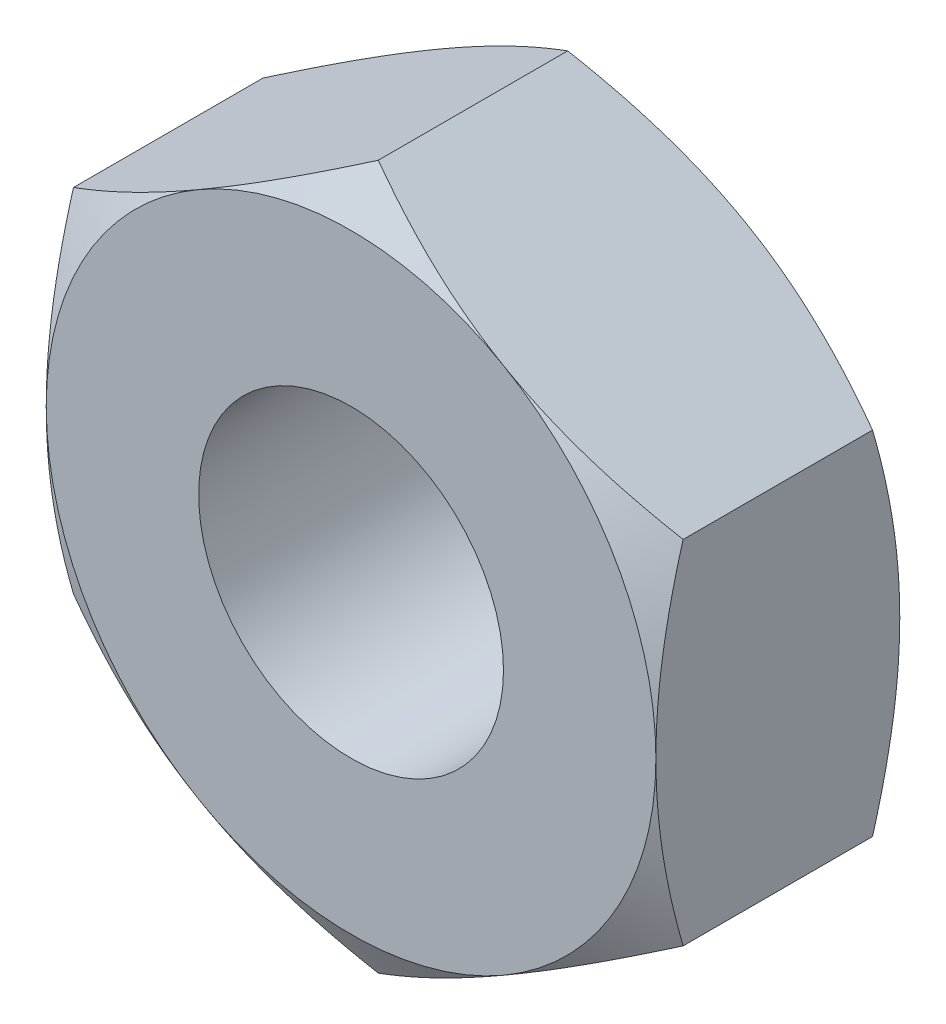
SolidWorks part; units mm, degrees
ref_plane "Front Plane" through (0, 0, 0) normal (0, 0, 1) x (1, 0, 0)
ref_plane "Top Plane" through (0, 0, 0) normal (0, 1, 0) x (1, 0, 0)
ref_plane "Right Plane" through (0, 0, 0) normal (1, 0, 0) x (0, 0, -1)
sketch "Sketch1" plane through (0, 0, 0) normal (1, 0, 0) x (0, 0, -1)
  line L0 (-1, 0) -> (1, 0) construction
  line L1 (-1, -2.5) -> (-1, 2.5) construction
  line L2 (1, -2.5) -> (1, 2.5) construction
  line L3 (-1, -1.25) -> (-1, 1.25) construction
  line L4 (-1.4219, 1.2987) -> (-1.1969, 0.909) construction
  line L5 (-1.1969, 0.909) -> (-0.9719, 1.2987) construction
  line L6 (-0.9719, 1.2987) -> (-1.4219, 1.2987) construction
  line L7 (-1.4078, 1.2744) -> (-0.9859, 1.2744) construction
  line L8 (-1.3938, 1.25) -> (-1, 1.25) construction
  line L9 (-1.225, 0.9577) -> (-1.1688, 0.9577) construction
  line L10 (-1.1969, 0.9577) -> (-1.1969, 0.909) construction
  line L11 (-1.1969, 1.2987) -> (-1.1969, 1.25) construction
  point P4 (0, 0)
  point P7 (-1, 0)
  point P11 (1, 0)
  point P14 (-1, 0)
  point P26 (-1.1969, 1.2744)
  point P27 (-1, -1.25)
  dimension "Height" = 2
  dimension "Width" = 5
  dimension "Thread OD" = 2.5
  dimension "D1" = 60
  dimension "Pitch" = 0.45
  dimension "D2" = 0.0562
sketch "Sketch2" plane through (0, 0, 0) normal (0, 0, 1) x (1, 0, 0)
  line L1 (0, 2.8868) -> (-2.5, 1.4434)
  line L2 (-2.5, 1.4434) -> (-2.5, -1.4434)
  line L3 (-2.5, -1.4434) -> (0, -2.8868)
  line L4 (0, -2.8868) -> (2.5, -1.4434)
  line L5 (2.5, -1.4434) -> (2.5, 1.4434)
  line L6 (2.5, 1.4434) -> (0, 2.8868)
  circle A0 centre (0, 0) radius 2.5 construction
  circle A1 centre (0, 0) radius 1.25
extrude "Boss-Extrude1" add sketch "Sketch2" along normal up to vertex (1 mm away) and the other way up to vertex (1 mm away) up to point (0, -2.5, 1) other way up to point (0, -2.5, -1)
sketch "Sketch3" plane through (0, 0, 1) normal (0, 0, 1) x (1, 0, 0)
  circle A0 centre (0, 0) radius 2.5
extrude "Cut-Extrude1" cut sketch "Sketch3" against normal through all draft 60 flip side to cut
mirror "Mirror1" about plane through (0, 0, 0) normal (0, 0, 1) of "Cut-Extrude1"
ref_axis "Center Axis 1" through (0, 0, -10.9016) along (0, 0, 1)
ref_plane "Contact Plane 1" through (0, 0, 1) normal (0, 0, 1) x (1, 0, 0)
ref_plane "Contact Plane 2" through (0, 0, -1) normal (0, 0, -1) x (-1, 0, 0)
sketch "Sketch5" plane through (0, 0, 1) normal (0, 0, 1) x (1, 0, 0)
  circle A0 centre (0, 0) radius 1.25 construction
  circle A1 centre (0, 0) radius 1.25
curve "Helix/Spiral1" pitch 0.45 height 2.45 turns 5.4444
equation "\"D2@Sketch1\"=\"Pitch@Sketch1\"/8"
equation "\"D4@Helix/Spiral1\"=\"Pitch@Sketch1\""
equation "\"D3@Helix/Spiral1\"=\"Height@Sketch1\"+\"Pitch@Sketch1\""
